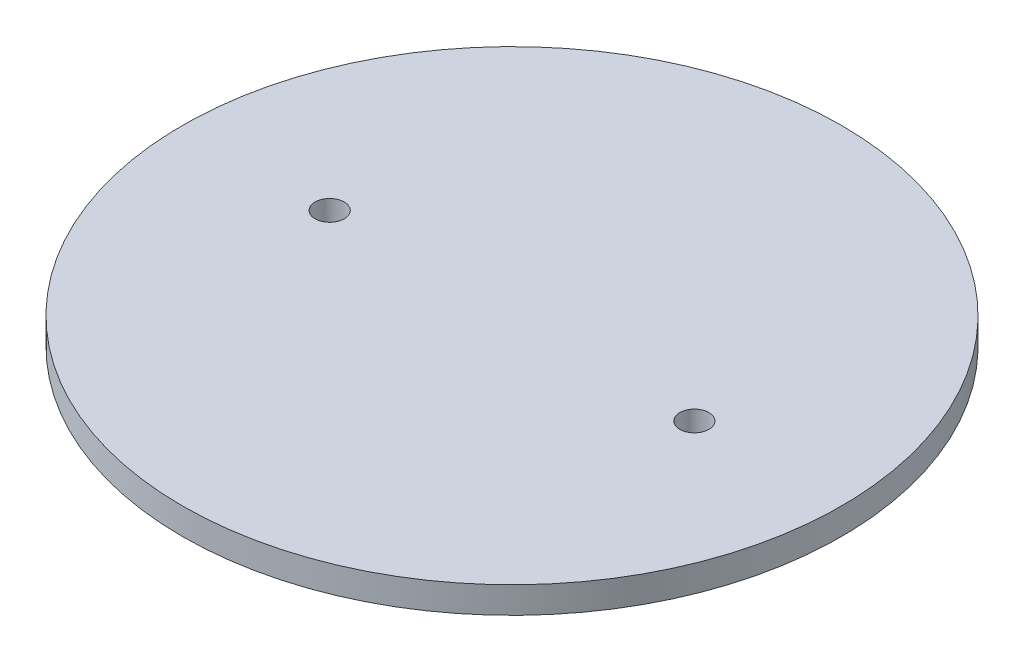
SolidWorks part; units mm, degrees
material "Balsa"
ref_plane "Front Plane" through (0, 0, 0) normal (0, 0, 1) x (1, 0, 0)
ref_plane "Top Plane" through (0, 0, 0) normal (0, 1, 0) x (1, 0, 0)
ref_plane "Right Plane" through (0, 0, 0) normal (1, 0, 0) x (0, 0, -1)
sketch "Sketch1" plane through (0, 0, 0) normal (0, 1, 0) x (1, 0, 0)
  line L0 (-49.7, 0) -> (49.7, 0) construction
  line L1 (0, 49.7) -> (0, -49.7) construction
  line L2 (49.7, 84.8597) -> (49.7, -119.3895) construction
  circle A0 centre (0, 0) radius 49.7
  circle A1 centre (-27.5, 0) radius 2.2
  circle A2 centre (27.5, 0) radius 2.2
  dimension "D1" = 55
  dimension "D2" = 4.4
  dimension "D3" = 99.4
extrude "Boss-Extrude1" add sketch "Sketch1" along normal blind 4
